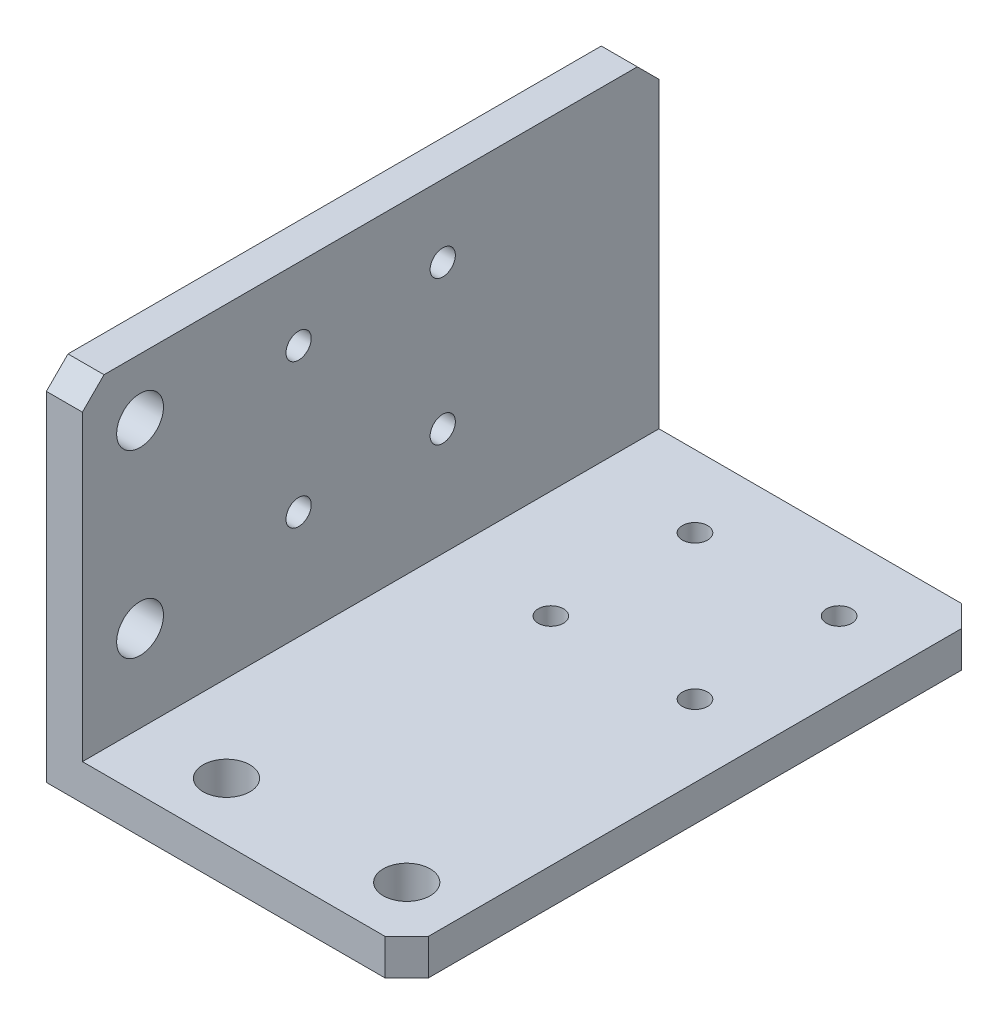
SolidWorks part; units mm, degrees
material "Lega 1060"
ref_plane "Piano frontale" through (0, 0, 0) normal (0, 0, 1) x (1, 0, 0)
ref_plane "Piano superiore" through (0, 0, 0) normal (0, 1, 0) x (1, 0, 0)
ref_plane "Piano destro" through (0, 0, 0) normal (1, 0, 0) x (0, 0, -1)
sketch "Schizzo1" plane through (0, 0, 0) normal (0, 0, 1) x (1, 0, 0)
  line L0 (0, 0) -> (0, 50)
  line L1 (0, 50) -> (5, 50)
  line L2 (5, 50) -> (5, 5)
  line L3 (5, 5) -> (50, 5)
  line L4 (50, 5) -> (50, 0)
  line L5 (50, 0) -> (0, 0)
  dimension "D1" = 5
  dimension "D2" = 5
  dimension "D3" = 50
  dimension "D4" = 50
extrude "Estrusione-Estrusione1" add sketch "Schizzo1" along normal blind 80
sketch "Schizzo2" plane through (0, 0, 0) normal (0, -1, 0) x (1, 0, 0)
  line L0 (5.4524, 72) -> (42.7933, 72) construction
  line L1 (0, 80) -> (50, 80) construction
  line L5 (50, 80) -> (50, 0) construction
  point P4 (17, 72)
  point P5 (42, 72)
  dimension "D1" = 8
  dimension "D2" = 25
  dimension "D3" = 8
sketch "Schizzo3" plane through (0, 0, 0) normal (-1, 0, 0) x (0, 0, 1)
  line L0 (72, 44.621) -> (72, 5.772) construction
  line L1 (80, 50) -> (80, 0) construction
  line L2 (80, 50) -> (0, 50) construction
  point P4 (72, 42)
  point P5 (72, 17)
  dimension "D1" = 8
  dimension "D2" = 8
  dimension "D3" = 25
hole_wizard "Foro Ø6.5 (6.5)-1" positions "Schizzo5" profile "Schizzo4" hole size "Ø6.5" standard "ISO" end condition through all
sketch "Schizzo5" plane through (0, 0, 0) normal (0, -1, 0) x (-1, 0, 0)
  point P0 (-17, -72)
  point P3 (-42, -72)
sketch "Schizzo4" plane through (17, 0, 72) normal (1, 0, 0) x (0, 0, -1)
  line L0 (0, 0) -> (0, 50)
  line L1 (0, 50) -> (3.25, 50)
  line L2 (3.25, 50) -> (3.25, 0)
  line L5 (3.25, 0) -> (0, 0)
  line L11 (0, -6.35) -> (0, 107.95) construction
  dimension "Thru Hole Dia." = 6.5
  dimension "Thru Hole Depth" = 50
hole_wizard "Foro Ø6.5 (6.5)-2" positions "Schizzo7" profile "Schizzo6" hole size "Ø6.5" standard "ISO"
sketch "Schizzo7" plane through (0, 0, 0) normal (-1, 0, 0) x (0, 0, 1)
  point P1 (72, 42)
  point P4 (72, 17)
sketch "Schizzo6" plane through (0, 42, 72) normal (0, 1, 0) x (0, 0, 1)
  line L0 (0, 0) -> (0, 6.9528)
  line L1 (0, 6.9528) -> (3.25, 5)
  line L2 (3.25, 5) -> (3.25, 0)
  line L5 (3.25, 0) -> (0, 0)
  line L10 (0, 6.9528) -> (-3.25, 5) construction
  line L11 (0, -6.35) -> (0, 107.95) construction
  dimension "Hole Dia." = 6.5
  dimension "Hole Depth" = 5
  dimension "Drill Angle" = 118
ref_plane "Piano1" through (0, 0, 40) normal (0, 0, 1) x (1, 0, 0)
sketch "Schizzo8" plane through (0, 0, 0) normal (0, -1, 0) x (1, 0, 0)
  line L0 (30, 20) -> (7.0316, 20) construction
  line L1 (30, 20) -> (22.8949, 12.8949) construction
  line L2 (0, 80) -> (50, 80) construction
  line L3 (50, 80) -> (50, 0) construction
  circle A0 centre (20, 10) radius 1.75
  circle A1 centre (20, 30) radius 1.75
  circle A2 centre (40, 30) radius 1.75
  circle A3 centre (40, 10) radius 1.75
  point P18 (30, 20)
  dimension "D3" = 3.5
  dimension "D1" = 60
  dimension "D2" = 20
  dimension "D4" = 45
  dimension "D5" = 20
  dimension "D6" = 4
extrude "Taglio-Estrusione1" cut sketch "Schizzo8" against normal up to next
sketch "Schizzo9" plane through (0, 0, 0) normal (-1, 0, 0) x (0, 0, 1)
  line L0 (40, 44.574) -> (40, 30) construction
  line L1 (40, 30) -> (33.014, 36.986) construction
  line L2 (80, 50) -> (0, 50) construction
  line L3 (80, 50) -> (80, 0) construction
  circle A0 centre (30, 40) radius 1.75
  circle A1 centre (50, 40) radius 1.75
  circle A2 centre (50, 20) radius 1.75
  circle A3 centre (30, 20) radius 1.75
  point P18 (40, 30)
  dimension "D4" = 3.5
  dimension "D1" = 20
  dimension "D2" = 40
  dimension "D3" = 45
  dimension "D5" = 20
  dimension "D6" = 4
extrude "Taglio-Estrusione2" cut sketch "Schizzo9" against normal up to next
chamfer "Smusso1" distance 3 angle 45 4 edges at (2.5, 50, 0) (50, 2.5, 0) (50, 2.5, 80) (2.5, 50, 80)
